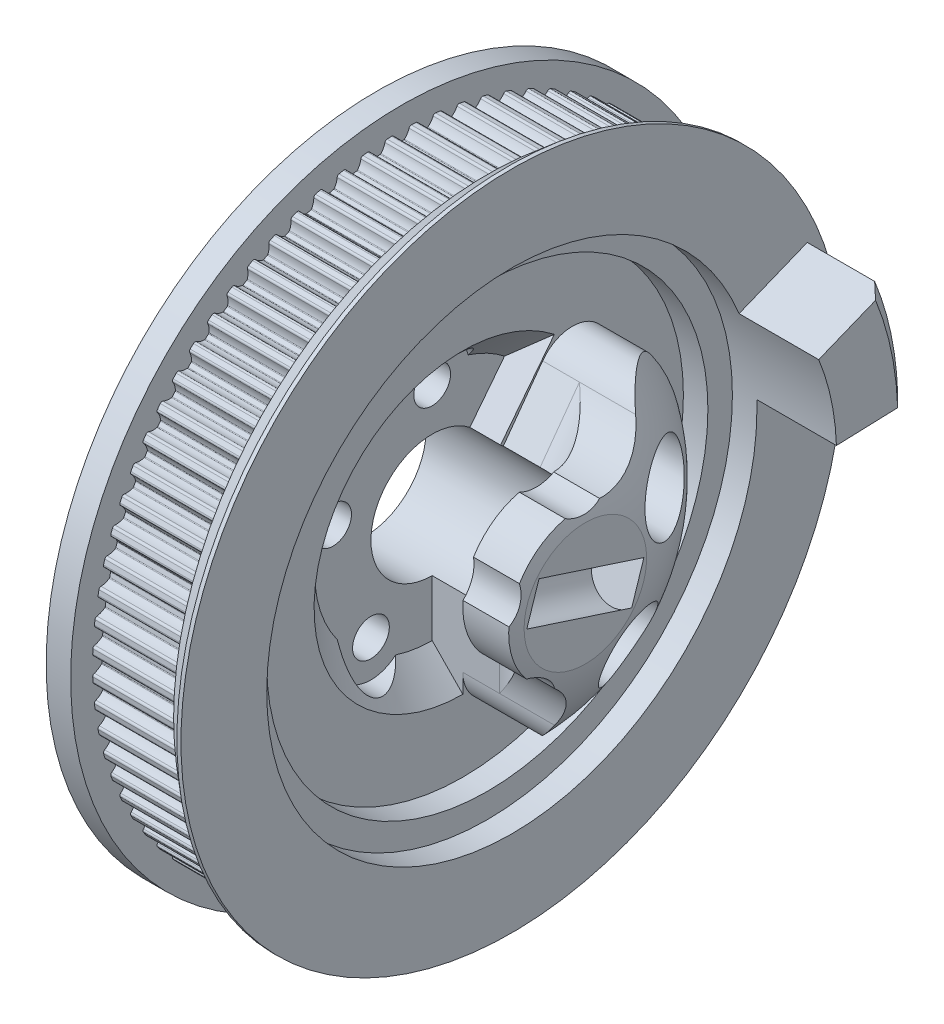
SolidWorks part; units mm, degrees
ref_plane "Front Plane" through (0, 0, 0) normal (0, 0, 1) x (1, 0, 0)
ref_plane "Top Plane" through (0, 0, 0) normal (0, 1, 0) x (1, 0, 0)
ref_plane "Right Plane" through (0, 0, 0) normal (1, 0, 0) x (0, 0, -1)
sketch "Sketch1" plane through (0, 0, 0) normal (0, 1, 0) x (1, 0, 0)
  line L0 (0, 5) -> (0, 15.5)
  line L1 (0, 15.5) -> (4, 15.5)
  line L2 (1, 23) -> (1, 27)
  line L3 (1, 27) -> (3, 27)
  line L4 (3, 27) -> (3, 23)
  line L5 (3, 23) -> (10, 23)
  line L6 (10, 23) -> (10, 27)
  line L7 (10, 27) -> (12, 27)
  line L8 (12, 27) -> (12, 20)
  line L11 (26, 0) -> (0, 0) construction
  line L12 (0, 5) -> (8, 5)
  line L13 (0, 0) -> (0, 5) construction
  line L14 (12, 20) -> (10, 20)
  line L15 (8, 18) -> (8, 5)
  line L17 (4, 15.5) -> (4, 21.3623)
  line L19 (1, 23) -> (1, 22.2508)
  line L20 (1, 22.2508) -> (4, 21.3623)
  arc A0 (10, 20) -> (8, 18) centre (10, 18) ccw
  point P17 (8, 20)
  dimension "D11" = 2
  dimension "D1" = 15.5
  dimension "D2" = 4
  dimension "D3" = 27
  dimension "D4" = 2
  dimension "D5" = 7
  dimension "D6" = 2
  dimension "D7" = 23
  dimension "D8" = 10
  dimension "D9" = 15
  dimension "D10" = 4
  dimension "D12" = 8
revolve "Revolve1" add sketch "Sketch1" angle 360 about L11
sketch "Sketch2" plane through (12, 0, 0) normal (1, 0, 0) x (0, 0, -1)
  line L0 (0, 0) -> (0, 8.5) construction
  circle A0 centre (0, 8.5) radius 1.5
  circle A1 centre (8.084, 2.6266) radius 1.5
  circle A2 centre (4.9962, -6.8766) radius 1.5
  circle A3 centre (-4.9962, -6.8766) radius 1.5
  circle A4 centre (-8.084, 2.6266) radius 1.5
  point P15 (0, 0)
  dimension "D2" = 3
  dimension "D1" = 8.5
extrude "Cut-Extrude1" cut sketch "Sketch2" against normal through all
chamfer "Chamfer1" distance 1 angle 45 1 edges at (0, 0, -15.5)
sketch "Sketch3" plane through (8, 0, 0) normal (1, 0, 0) x (0, 0, -1)
  circle A0 centre (0, 8.5) radius 3
  circle A1 centre (8.084, 2.6266) radius 3
  circle A2 centre (4.9962, -6.8766) radius 3
  circle A3 centre (-4.9962, -6.8766) radius 3
  circle A4 centre (-8.084, 2.6266) radius 3
  point P14 (0, 0)
  dimension "D1" = 6
extrude "Cut-Extrude2" cut sketch "Sketch3" against normal blind 2.5
sketch "Sketch4" plane through (8, 0, 0) normal (1, 0, 0) x (0, 0, -1)
  line L0 (3.3089, 3.7485) -> (6.518, 8.1654)
  line L1 (0, 9.099) -> (-8.6536, 2.8117) construction
  line L2 (-8.6536, 2.8117) -> (-5.3482, -7.3612) construction
  line L3 (-5.3482, -7.3612) -> (5.3482, -7.3612) construction
  line L4 (5.3482, -7.3612) -> (8.6536, 2.8117) construction
  line L5 (8.6536, 2.8117) -> (0, 9.099) construction
  line L6 (0, -5) -> (0, -10.583)
  circle A0 centre (0, 0) radius 7.3612 construction
  arc A1 (0, -5) -> (3.3089, 3.7485) centre (0, 0) ccw
  arc A2 (3.8182, -13.4693) -> (11.3846, 8.148) centre (0, 0) ccw
  arc A3 (0, -10.583) -> (3.8182, -13.4693) centre (3, -10.583) ccw
  arc A4 (6.518, 8.1654) -> (11.3846, 8.148) centre (8.9451, 6.402) cw
  circle A5 centre (0, 0) radius 5 construction
  point P14 (0, -14)
  dimension "D1" = 28
  dimension "D2" = 3
extrude "Boss-Extrude1" add sketch "Sketch4" along normal blind 6
sketch "Sketch5" plane through (14, 0, 0) normal (1, 0, 0) x (0, 0, -1)
  line L2 (6.518, 8.1654) -> (3.3089, 3.7485)
  line L3 (0, -5) -> (0, -10.583)
  arc A2 (1.0026, 5.9156) -> (-3.0811, -5.1485) centre (0, 0) ccw
  arc A3 (1.0026, 5.9156) -> (6.518, 8.1654) centre (1.9467, 11.4866) ccw
  arc A5 (-3.0811, -5.1485) -> (0, -10.583) centre (-6.3333, -10.583) cw
  arc A7 (0, -10.583) -> (3.8182, -13.4693) centre (3, -10.583) ccw
  arc A8 (3.8182, -13.4693) -> (11.3846, 8.148) centre (0, 0) ccw
  arc A9 (11.3846, 8.148) -> (6.518, 8.1654) centre (8.9451, 6.402) ccw
  arc A10 (0, -5) -> (3.3089, 3.7485) centre (0, 0) ccw
  arc A11 (0, -10.583) -> (3.8182, -13.4693) centre (3, -10.583) ccw
  arc A12 (3.8182, -13.4693) -> (11.3846, 8.148) centre (0, 0) ccw
  arc A13 (11.3846, 8.148) -> (6.518, 8.1654) centre (8.9451, 6.402) ccw
  dimension "D2" = 6
  dimension "D1" = 0
extrude "Boss-Extrude2" add sketch "Sketch5" along normal blind 4
sketch "Sketch7" plane through (18, 0, 0) normal (1, 0, 0) x (0, 0, -1)
  circle A0 centre (8.084, 2.6266) radius 1.5
  circle A1 centre (4.9962, -6.8766) radius 1.5
extrude "Cut-Extrude4" cut sketch "Sketch7" against normal through all
sketch "Sketch8" plane through (18, 0, 0) normal (1, 0, 0) x (0, 0, -1)
  circle A0 centre (8.084, 2.6266) radius 3
  circle A1 centre (4.9962, -6.8766) radius 3
  circle A2 centre (0, 8.5) radius 3
  circle A3 centre (-8.084, 2.6266) radius 3
  circle A4 centre (-4.9962, -6.8766) radius 3
  dimension "D1" = 6
  dimension "D2" = 6
  dimension "D3" = 6
  dimension "D4" = 6
  dimension "D5" = 6
extrude "Cut-Extrude5" cut sketch "Sketch8" against normal up to surface (12.5 mm away) up to face at (5.5, 8.5, -3)
sketch "Sketch9" plane through (0, 0, 0) normal (0, 1, 0) x (1, 0, 0)
  line L0 (0, 0) -> (18, 0) construction
  line L2 (18, 14) -> (8, 14) construction
  line L3 (12, 14) -> (18, 14)
  line L4 (18, 3.8182) -> (18, 14) construction
  line L5 (18, 14) -> (18, 5)
  arc A0 (12, 14) -> (18, 5) centre (3.5423, 1.8615) cw
  dimension "D1" = 9
  dimension "D2" = 6
revolve "Cut-Revolve1" cut sketch "Sketch9" angle 360 about L0
sketch "Sketch10" plane through (10, 0, 0) normal (-1, 0, 0) x (0, 0, 1)
  line L0 (0.1734, 24.4504) -> (-0.1734, 24.4504)
  line L1 (-0.8032, 25.1982) -> (-1.1763, 25.1835)
  line L2 (-1.7455, 24.3886) -> (-2.0913, 24.3614)
  line L3 (-2.7777, 25.0575) -> (-3.1486, 25.0136)
  line L4 (-3.6536, 24.1765) -> (-3.9962, 24.1222)
  line L5 (-4.7352, 24.7623) -> (-5.1014, 24.6895)
  line L6 (-5.5392, 23.8153) -> (-5.8765, 23.7343)
  line L7 (-6.6634, 24.3145) -> (-7.0228, 24.2131)
  line L8 (-7.3906, 23.3073) -> (-7.7205, 23.2001)
  line L9 (-8.5505, 23.7167) -> (-8.9009, 23.5875)
  line L10 (-9.1965, 22.6556) -> (-9.517, 22.5228)
  line L11 (-10.385, 22.9727) -> (-10.7241, 22.8164)
  line L12 (-10.9457, 21.8642) -> (-11.2548, 21.7067)
  line L13 (-12.1554, 22.0871) -> (-12.4812, 21.9047)
  line L14 (-12.6274, 20.938) -> (-12.9232, 20.7568)
  line L15 (-13.8508, 21.0653) -> (-14.1614, 20.8579)
  line L16 (-14.2313, 19.8827) -> (-14.5119, 19.6788)
  line L17 (-15.4609, 19.9137) -> (-15.7542, 19.6825)
  line L18 (-15.7474, 18.7049) -> (-16.0111, 18.4796)
  line L19 (-16.9757, 18.6392) -> (-17.2499, 18.3858)
  line L20 (-17.1664, 17.4117) -> (-17.4117, 17.1664)
  line L21 (-18.3858, 17.2499) -> (-18.6392, 16.9757)
  line L22 (-18.4796, 16.0111) -> (-18.7049, 15.7474)
  line L23 (-19.6825, 15.7542) -> (-19.9137, 15.4609)
  line L24 (-19.6788, 14.5119) -> (-19.8827, 14.2313)
  line L25 (-20.8579, 14.1614) -> (-21.0653, 13.8508)
  line L26 (-20.7568, 12.9232) -> (-20.938, 12.6274)
  line L27 (-21.9047, 12.4812) -> (-22.0871, 12.1554)
  line L28 (-21.7067, 11.2548) -> (-21.8642, 10.9457)
  line L29 (-22.8164, 10.7241) -> (-22.9727, 10.385)
  line L30 (-22.5228, 9.517) -> (-22.6556, 9.1965)
  line L31 (-23.5875, 8.9009) -> (-23.7167, 8.5505)
  line L32 (-23.2001, 7.7205) -> (-23.3073, 7.3906)
  line L33 (-24.2131, 7.0228) -> (-24.3145, 6.6634)
  line L34 (-23.7343, 5.8765) -> (-23.8153, 5.5392)
  line L35 (-24.6895, 5.1014) -> (-24.7623, 4.7352)
  line L36 (-24.1222, 3.9962) -> (-24.1765, 3.6536)
  line L37 (-25.0136, 3.1486) -> (-25.0575, 2.7777)
  line L38 (-24.3614, 2.0913) -> (-24.3886, 1.7455)
  line L39 (-25.1835, 1.1763) -> (-25.1982, 0.8032)
  line L40 (-24.4504, 0.1734) -> (-24.4504, -0.1734)
  line L41 (-25.1982, -0.8032) -> (-25.1835, -1.1763)
  line L42 (-24.3886, -1.7455) -> (-24.3614, -2.0913)
  line L43 (-25.0575, -2.7777) -> (-25.0136, -3.1486)
  line L44 (-24.1765, -3.6536) -> (-24.1222, -3.9962)
  line L45 (-24.7623, -4.7352) -> (-24.6895, -5.1014)
  line L46 (-23.8153, -5.5392) -> (-23.7343, -5.8765)
  line L47 (-24.3145, -6.6634) -> (-24.2131, -7.0228)
  line L48 (-23.3073, -7.3906) -> (-23.2001, -7.7205)
  line L49 (-23.7167, -8.5505) -> (-23.5875, -8.9009)
  line L50 (-22.6556, -9.1965) -> (-22.5228, -9.517)
  line L51 (-22.9727, -10.385) -> (-22.8164, -10.7241)
  line L52 (-21.8642, -10.9457) -> (-21.7067, -11.2548)
  line L53 (-22.0871, -12.1554) -> (-21.9047, -12.4812)
  line L54 (-20.938, -12.6274) -> (-20.7568, -12.9232)
  line L55 (-21.0653, -13.8508) -> (-20.8579, -14.1614)
  line L56 (-19.8827, -14.2313) -> (-19.6788, -14.5119)
  line L57 (-19.9137, -15.4609) -> (-19.6825, -15.7542)
  line L58 (-18.7049, -15.7474) -> (-18.4796, -16.0111)
  line L59 (-18.6392, -16.9757) -> (-18.3858, -17.2499)
  line L60 (-17.4117, -17.1664) -> (-17.1664, -17.4117)
  line L61 (-17.2499, -18.3858) -> (-16.9757, -18.6392)
  line L62 (-16.0111, -18.4796) -> (-15.7474, -18.7049)
  line L63 (-15.7542, -19.6825) -> (-15.4609, -19.9137)
  line L64 (-14.5119, -19.6788) -> (-14.2313, -19.8827)
  line L65 (-14.1614, -20.8579) -> (-13.8508, -21.0653)
  line L66 (-12.9232, -20.7568) -> (-12.6274, -20.938)
  line L67 (-12.4812, -21.9047) -> (-12.1554, -22.0871)
  line L68 (-11.2548, -21.7067) -> (-10.9457, -21.8642)
  line L69 (-10.7241, -22.8164) -> (-10.385, -22.9727)
  line L70 (-9.517, -22.5228) -> (-9.1965, -22.6556)
  line L71 (-8.9009, -23.5875) -> (-8.5505, -23.7167)
  line L72 (-7.7205, -23.2001) -> (-7.3906, -23.3073)
  line L73 (-7.0228, -24.2131) -> (-6.6634, -24.3145)
  line L74 (-5.8765, -23.7343) -> (-5.5392, -23.8153)
  line L75 (-5.1014, -24.6895) -> (-4.7352, -24.7623)
  line L76 (-3.9962, -24.1222) -> (-3.6536, -24.1765)
  line L77 (-3.1486, -25.0136) -> (-2.7777, -25.0575)
  line L78 (-2.0913, -24.3614) -> (-1.7455, -24.3886)
  line L79 (-1.1763, -25.1835) -> (-0.8032, -25.1982)
  line L80 (-0.1734, -24.4504) -> (0.1734, -24.4504)
  line L81 (0.8032, -25.1982) -> (1.1763, -25.1835)
  line L82 (1.7455, -24.3886) -> (2.0913, -24.3614)
  line L83 (2.7777, -25.0575) -> (3.1486, -25.0136)
  line L84 (3.6536, -24.1765) -> (3.9962, -24.1222)
  line L85 (4.7352, -24.7623) -> (5.1014, -24.6895)
  line L86 (5.5392, -23.8153) -> (5.8765, -23.7343)
  line L87 (6.6634, -24.3145) -> (7.0228, -24.2131)
  line L88 (7.3906, -23.3073) -> (7.7205, -23.2001)
  line L89 (8.5505, -23.7167) -> (8.9009, -23.5875)
  line L90 (9.1965, -22.6556) -> (9.517, -22.5228)
  line L91 (10.385, -22.9727) -> (10.7241, -22.8164)
  line L92 (10.9457, -21.8642) -> (11.2548, -21.7067)
  line L93 (12.1554, -22.0871) -> (12.4812, -21.9047)
  line L94 (12.6274, -20.938) -> (12.9232, -20.7568)
  line L95 (13.8508, -21.0653) -> (14.1614, -20.8579)
  line L96 (14.2313, -19.8827) -> (14.5119, -19.6788)
  line L97 (15.4609, -19.9137) -> (15.7542, -19.6825)
  line L98 (15.7474, -18.7049) -> (16.0111, -18.4796)
  line L99 (16.9757, -18.6392) -> (17.2499, -18.3858)
  line L100 (17.1664, -17.4117) -> (17.4117, -17.1664)
  line L101 (18.3858, -17.2499) -> (18.6392, -16.9757)
  line L102 (18.4796, -16.0111) -> (18.7049, -15.7474)
  line L103 (19.6825, -15.7542) -> (19.9137, -15.4609)
  line L104 (19.6788, -14.5119) -> (19.8827, -14.2313)
  line L105 (20.8579, -14.1614) -> (21.0653, -13.8508)
  line L106 (20.7568, -12.9232) -> (20.938, -12.6274)
  line L107 (21.9047, -12.4812) -> (22.0871, -12.1554)
  line L108 (21.7067, -11.2548) -> (21.8642, -10.9457)
  line L109 (22.8164, -10.7241) -> (22.9727, -10.385)
  line L110 (22.5228, -9.517) -> (22.6556, -9.1965)
  line L111 (23.5875, -8.9009) -> (23.7167, -8.5505)
  line L112 (23.2001, -7.7205) -> (23.3073, -7.3906)
  line L113 (24.2131, -7.0228) -> (24.3145, -6.6634)
  line L114 (23.7343, -5.8765) -> (23.8153, -5.5392)
  line L115 (24.6895, -5.1014) -> (24.7623, -4.7352)
  line L116 (24.1222, -3.9962) -> (24.1765, -3.6536)
  line L117 (25.0136, -3.1486) -> (25.0575, -2.7777)
  line L118 (24.3614, -2.0913) -> (24.3886, -1.7455)
  line L119 (25.1835, -1.1763) -> (25.1982, -0.8032)
  line L120 (24.4504, -0.1734) -> (24.4504, 0.1734)
  line L121 (25.1982, 0.8032) -> (25.1835, 1.1763)
  line L122 (24.3886, 1.7455) -> (24.3614, 2.0913)
  line L123 (25.0575, 2.7777) -> (25.0136, 3.1486)
  line L124 (24.1765, 3.6536) -> (24.1222, 3.9962)
  line L125 (24.7623, 4.7352) -> (24.6895, 5.1014)
  line L126 (23.8153, 5.5392) -> (23.7343, 5.8765)
  line L127 (24.3145, 6.6634) -> (24.2131, 7.0228)
  line L128 (23.3073, 7.3906) -> (23.2001, 7.7205)
  line L129 (23.7167, 8.5505) -> (23.5875, 8.9009)
  line L130 (22.6556, 9.1965) -> (22.5228, 9.517)
  line L131 (22.9727, 10.385) -> (22.8164, 10.7241)
  line L132 (21.8642, 10.9457) -> (21.7067, 11.2548)
  line L133 (22.0871, 12.1554) -> (21.9047, 12.4812)
  line L134 (20.938, 12.6274) -> (20.7568, 12.9232)
  line L135 (21.0653, 13.8508) -> (20.8579, 14.1614)
  line L136 (19.8827, 14.2313) -> (19.6788, 14.5119)
  line L137 (19.9137, 15.4609) -> (19.6825, 15.7542)
  line L138 (18.7049, 15.7474) -> (18.4796, 16.0111)
  line L139 (18.6392, 16.9757) -> (18.3858, 17.2499)
  line L140 (17.4117, 17.1664) -> (17.1664, 17.4117)
  line L141 (17.2499, 18.3858) -> (16.9757, 18.6392)
  line L142 (16.0111, 18.4796) -> (15.7474, 18.7049)
  line L143 (15.7542, 19.6825) -> (15.4609, 19.9137)
  line L144 (14.5119, 19.6788) -> (14.2313, 19.8827)
  line L145 (14.1614, 20.8579) -> (13.8508, 21.0653)
  line L146 (12.9232, 20.7568) -> (12.6274, 20.938)
  line L147 (12.4812, 21.9047) -> (12.1554, 22.0871)
  line L148 (11.2548, 21.7067) -> (10.9457, 21.8642)
  line L149 (10.7241, 22.8164) -> (10.385, 22.9727)
  line L150 (9.517, 22.5228) -> (9.1965, 22.6556)
  line L151 (8.9009, 23.5875) -> (8.5505, 23.7167)
  line L152 (7.7205, 23.2001) -> (7.3906, 23.3073)
  line L153 (7.0228, 24.2131) -> (6.6634, 24.3145)
  line L154 (5.8765, 23.7343) -> (5.5392, 23.8153)
  line L155 (5.1014, 24.6895) -> (4.7352, 24.7623)
  line L156 (3.9962, 24.1222) -> (3.6536, 24.1765)
  line L157 (3.1486, 25.0136) -> (2.7777, 25.0575)
  line L158 (2.0913, 24.3614) -> (1.7455, 24.3886)
  circle A0 centre (0, 0) radius 18
  arc A1 (0.8032, 25.1982) -> (0.6156, 25.0645) centre (0.7971, 25.0083) ccw
  arc A2 (0.2414, 24.4764) -> (0.6156, 25.0645) centre (-0.65, 25.4567) ccw
  arc A3 (0.1734, 24.4504) -> (0.2414, 24.4764) centre (0.1741, 24.5504) ccw
  arc A4 (-0.2414, 24.4764) -> (-0.1734, 24.4504) centre (-0.1741, 24.5504) ccw
  arc A5 (-0.6156, 25.0645) -> (-0.2414, 24.4764) centre (0.65, 25.4567) ccw
  arc A6 (-0.6156, 25.0645) -> (-0.8032, 25.1982) centre (-0.7971, 25.0083) ccw
  arc A7 (-1.1763, 25.1835) -> (-1.3528, 25.0356) centre (-1.1675, 24.9937) ccw
  arc A8 (-1.6797, 24.4199) -> (-1.3528, 25.0356) centre (-2.6453, 25.3272) ccw
  arc A9 (-1.7455, 24.3886) -> (-1.6797, 24.4199) centre (-1.7526, 24.4884) ccw
  arc A10 (-2.1611, 24.382) -> (-2.0913, 24.3614) centre (-2.0998, 24.461) ccw
  arc A11 (-2.5803, 24.939) -> (-2.1611, 24.382) centre (-1.3493, 25.4292) ccw
  arc A12 (-2.5803, 24.939) -> (-2.7777, 25.0575) centre (-2.7568, 24.8687) ccw
  arc A13 (-3.1486, 25.0136) -> (-3.3129, 24.8523) centre (-3.1249, 24.8251) ccw
  arc A14 (-3.5905, 24.2128) -> (-3.3129, 24.8523) centre (-4.6243, 25.0416) ccw
  arc A15 (-3.6536, 24.1765) -> (-3.5905, 24.2128) centre (-3.6685, 24.2754) ccw
  arc A16 (-4.0674, 24.1373) -> (-3.9962, 24.1222) centre (-4.0125, 24.2209) ccw
  arc A17 (-4.529, 24.6596) -> (-4.0674, 24.1373) centre (-3.3403, 25.245) ccw
  arc A18 (-4.529, 24.6596) -> (-4.7352, 24.7623) centre (-4.6995, 24.5757) ccw
  arc A19 (-5.1014, 24.6895) -> (-5.2526, 24.5157) centre (-5.063, 24.5034) ccw
  arc A20 (-5.4792, 23.8565) -> (-5.2526, 24.5157) centre (-6.5748, 24.6016) ccw
  arc A21 (-5.5392, 23.8153) -> (-5.4792, 23.8565) centre (-5.5618, 23.9127) ccw
  arc A22 (-5.9486, 23.7438) -> (-5.8765, 23.7343) centre (-5.9005, 23.8314) ccw
  arc A23 (-6.4498, 24.2283) -> (-5.9486, 23.7438) centre (-5.3107, 24.9051) ccw
  arc A24 (-6.4498, 24.2283) -> (-6.6634, 24.3145) centre (-6.6132, 24.1312) ccw
  arc A25 (-7.0228, 24.2131) -> (-7.1599, 24.028) centre (-6.9699, 24.0306) ccw
  arc A26 (-7.334, 23.353) -> (-7.1599, 24.028) centre (-8.4847, 24.0099) ccw
  arc A27 (-7.3906, 23.3073) -> (-7.334, 23.353) centre (-7.4209, 23.4026) ccw
  arc A28 (-7.7932, 23.2038) -> (-7.7205, 23.2001) centre (-7.7521, 23.295) ccw
  arc A29 (-8.3309, 23.6475) -> (-7.7932, 23.2038) centre (-7.2484, 24.4116) ccw
  arc A30 (-8.3309, 23.6475) -> (-8.5505, 23.7167) centre (-8.4861, 23.538) ccw
  arc A31 (-8.9009, 23.5875) -> (-9.023, 23.3922) centre (-8.8338, 23.4097) ccw
  arc A32 (-9.1437, 22.7056) -> (-9.023, 23.3922) centre (-10.3424, 23.2702) ccw
  arc A33 (-9.1965, 22.6556) -> (-9.1437, 22.7056) centre (-9.2341, 22.7482) ccw
  arc A34 (-9.5898, 22.5209) -> (-9.517, 22.5228) centre (-9.5559, 22.615) ccw
  arc A35 (-10.1606, 22.921) -> (-9.5898, 22.5209) centre (-9.1413, 23.7677) ccw
  arc A36 (-10.1606, 22.921) -> (-10.385, 22.9727) centre (-10.3067, 22.7996) ccw
  arc A37 (-10.7241, 22.8164) -> (-10.8305, 22.6122) centre (-10.6433, 22.6444) ccw
  arc A38 (-10.8969, 21.9182) -> (-10.8305, 22.6122) centre (-12.1363, 22.387) ccw
  arc A39 (-10.9457, 21.8642) -> (-10.8969, 21.9182) centre (-10.9905, 21.9536) ccw
  arc A40 (-11.3272, 21.699) -> (-11.2548, 21.7067) centre (-11.3008, 21.7955) ccw
  arc A41 (-11.9276, 22.0532) -> (-11.3272, 21.699) centre (-10.9779, 22.9772) ccw
  arc A42 (-11.9276, 22.0532) -> (-12.1554, 22.0871) centre (-12.0638, 21.9207) ccw
  arc A43 (-12.4812, 21.9047) -> (-12.5713, 21.6927) centre (-12.3871, 21.7396) ccw
  arc A44 (-12.583, 20.9957) -> (-12.5713, 21.6927) centre (-13.8553, 21.3658) ccw
  arc A45 (-12.6274, 20.938) -> (-12.583, 20.9957) centre (-12.6791, 21.0236) ccw
  arc A46 (-12.9947, 20.7434) -> (-12.9232, 20.7568) centre (-12.976, 20.8417) ccw
  arc A47 (-13.6211, 21.0494) -> (-12.9947, 20.7434) centre (-12.7469, 22.045) ccw
  arc A48 (-13.6211, 21.0494) -> (-13.8508, 21.0653) centre (-13.7465, 20.9066) ccw
  arc A49 (-14.1614, 20.8579) -> (-14.2345, 20.6395) centre (-14.0546, 20.7007) ccw
  arc A50 (-14.1916, 19.9437) -> (-14.2345, 20.6395) centre (-15.4889, 20.2128) ccw
  arc A51 (-14.2313, 19.8827) -> (-14.1916, 19.9437) centre (-14.2895, 19.964) ccw
  arc A52 (-14.5822, 19.6599) -> (-14.5119, 19.6788) centre (-14.5712, 19.7593) ccw
  arc A53 (-15.2306, 19.9158) -> (-14.5822, 19.6599) centre (-14.4372, 20.977) ccw
  arc A54 (-15.2306, 19.9158) -> (-15.4609, 19.9137) centre (-15.3444, 19.7636) ccw
  arc A55 (-15.7542, 19.6825) -> (-15.81, 19.459) centre (-15.6355, 19.5341) ccw
  arc A56 (-15.7126, 18.7688) -> (-15.81, 19.459) centre (-17.0271, 18.9353) ccw
  arc A57 (-15.7474, 18.7049) -> (-15.7126, 18.7688) centre (-15.8118, 18.7814) ccw
  arc A58 (-16.0797, 18.4552) -> (-16.0111, 18.4796) centre (-16.0766, 18.5552) ccw
  arc A59 (-16.7462, 18.6594) -> (-16.0797, 18.4552) centre (-16.0385, 19.7796) ccw
  arc A60 (-16.7462, 18.6594) -> (-16.9757, 18.6392) centre (-16.8477, 18.4988) ccw
  arc A61 (-17.2499, 18.3858) -> (-17.288, 18.1586) centre (-17.1199, 18.2472) ccw
  arc A62 (-17.1367, 17.4781) -> (-17.288, 18.1586) centre (-18.4602, 17.541) ccw
  arc A63 (-17.1664, 17.4117) -> (-17.1367, 17.4781) centre (-17.2366, 17.4829) ccw
  arc A64 (-17.4781, 17.1367) -> (-17.4117, 17.1664) centre (-17.4829, 17.2366) ccw
  arc A65 (-18.1586, 17.288) -> (-17.4781, 17.1367) centre (-17.541, 18.4602) ccw
  arc A66 (-18.1586, 17.288) -> (-18.3858, 17.2499) centre (-18.2472, 17.1199) ccw
  arc A67 (-18.6392, 16.9757) -> (-18.6594, 16.7462) centre (-18.4988, 16.8477) ccw
  arc A68 (-18.4552, 16.0797) -> (-18.6594, 16.7462) centre (-19.7796, 16.0385) ccw
  arc A69 (-18.4796, 16.0111) -> (-18.4552, 16.0797) centre (-18.5552, 16.0766) ccw
  arc A70 (-18.7688, 15.7126) -> (-18.7049, 15.7474) centre (-18.7814, 15.8118) ccw
  arc A71 (-19.459, 15.81) -> (-18.7688, 15.7126) centre (-18.9353, 17.0271) ccw
  arc A72 (-19.459, 15.81) -> (-19.6825, 15.7542) centre (-19.5341, 15.6355) ccw
  arc A73 (-19.9137, 15.4609) -> (-19.9158, 15.2306) centre (-19.7636, 15.3444) ccw
  arc A74 (-19.6599, 14.5822) -> (-19.9158, 15.2306) centre (-20.977, 14.4372) ccw
  arc A75 (-19.6788, 14.5119) -> (-19.6599, 14.5822) centre (-19.7593, 14.5712) ccw
  arc A76 (-19.9437, 14.1916) -> (-19.8827, 14.2313) centre (-19.964, 14.2895) ccw
  arc A77 (-20.6395, 14.2345) -> (-19.9437, 14.1916) centre (-20.2128, 15.4889) ccw
  arc A78 (-20.6395, 14.2345) -> (-20.8579, 14.1614) centre (-20.7007, 14.0546) ccw
  arc A79 (-21.0653, 13.8508) -> (-21.0494, 13.6211) centre (-20.9066, 13.7465) ccw
  arc A80 (-20.7434, 12.9947) -> (-21.0494, 13.6211) centre (-22.045, 12.7469) ccw
  arc A81 (-20.7568, 12.9232) -> (-20.7434, 12.9947) centre (-20.8417, 12.976) ccw
  arc A82 (-20.9957, 12.583) -> (-20.938, 12.6274) centre (-21.0236, 12.6791) ccw
  arc A83 (-21.6927, 12.5713) -> (-20.9957, 12.583) centre (-21.3658, 13.8553) ccw
  arc A84 (-21.6927, 12.5713) -> (-21.9047, 12.4812) centre (-21.7396, 12.3871) ccw
  arc A85 (-22.0871, 12.1554) -> (-22.0532, 11.9276) centre (-21.9207, 12.0638) ccw
  arc A86 (-21.699, 11.3272) -> (-22.0532, 11.9276) centre (-22.9772, 10.9779) ccw
  arc A87 (-21.7067, 11.2548) -> (-21.699, 11.3272) centre (-21.7955, 11.3008) ccw
  arc A88 (-21.9182, 10.8969) -> (-21.8642, 10.9457) centre (-21.9536, 10.9905) ccw
  arc A89 (-22.6122, 10.8305) -> (-21.9182, 10.8969) centre (-22.387, 12.1363) ccw
  arc A90 (-22.6122, 10.8305) -> (-22.8164, 10.7241) centre (-22.6444, 10.6433) ccw
  arc A91 (-22.9727, 10.385) -> (-22.921, 10.1606) centre (-22.7996, 10.3067) ccw
  arc A92 (-22.5209, 9.5898) -> (-22.921, 10.1606) centre (-23.7677, 9.1413) ccw
  arc A93 (-22.5228, 9.517) -> (-22.5209, 9.5898) centre (-22.615, 9.5559) ccw
  arc A94 (-22.7056, 9.1437) -> (-22.6556, 9.1965) centre (-22.7482, 9.2341) ccw
  arc A95 (-23.3922, 9.023) -> (-22.7056, 9.1437) centre (-23.2702, 10.3424) ccw
  arc A96 (-23.3922, 9.023) -> (-23.5875, 8.9009) centre (-23.4097, 8.8338) ccw
  arc A97 (-23.7167, 8.5505) -> (-23.6475, 8.3309) centre (-23.538, 8.4861) ccw
  arc A98 (-23.2038, 7.7932) -> (-23.6475, 8.3309) centre (-24.4116, 7.2484) ccw
  arc A99 (-23.2001, 7.7205) -> (-23.2038, 7.7932) centre (-23.295, 7.7521) ccw
  arc A100 (-23.353, 7.334) -> (-23.3073, 7.3906) centre (-23.4026, 7.4209) ccw
  arc A101 (-24.028, 7.1599) -> (-23.353, 7.334) centre (-24.0099, 8.4847) ccw
  arc A102 (-24.028, 7.1599) -> (-24.2131, 7.0228) centre (-24.0306, 6.9699) ccw
  arc A103 (-24.3145, 6.6634) -> (-24.2283, 6.4498) centre (-24.1312, 6.6132) ccw
  arc A104 (-23.7438, 5.9486) -> (-24.2283, 6.4498) centre (-24.9051, 5.3107) ccw
  arc A105 (-23.7343, 5.8765) -> (-23.7438, 5.9486) centre (-23.8314, 5.9005) ccw
  arc A106 (-23.8565, 5.4792) -> (-23.8153, 5.5392) centre (-23.9127, 5.5618) ccw
  arc A107 (-24.5157, 5.2526) -> (-23.8565, 5.4792) centre (-24.6016, 6.5748) ccw
  arc A108 (-24.5157, 5.2526) -> (-24.6895, 5.1014) centre (-24.5034, 5.063) ccw
  arc A109 (-24.7623, 4.7352) -> (-24.6596, 4.529) centre (-24.5757, 4.6995) ccw
  arc A110 (-24.1373, 4.0674) -> (-24.6596, 4.529) centre (-25.245, 3.3403) ccw
  arc A111 (-24.1222, 3.9962) -> (-24.1373, 4.0674) centre (-24.2209, 4.0125) ccw
  arc A112 (-24.2128, 3.5905) -> (-24.1765, 3.6536) centre (-24.2754, 3.6685) ccw
  arc A113 (-24.8523, 3.3129) -> (-24.2128, 3.5905) centre (-25.0416, 4.6243) ccw
  arc A114 (-24.8523, 3.3129) -> (-25.0136, 3.1486) centre (-24.8251, 3.1249) ccw
  arc A115 (-25.0575, 2.7777) -> (-24.939, 2.5803) centre (-24.8687, 2.7568) ccw
  arc A116 (-24.382, 2.1611) -> (-24.939, 2.5803) centre (-25.4292, 1.3493) ccw
  arc A117 (-24.3614, 2.0913) -> (-24.382, 2.1611) centre (-24.461, 2.0998) ccw
  arc A118 (-24.4199, 1.6797) -> (-24.3886, 1.7455) centre (-24.4884, 1.7526) ccw
  arc A119 (-25.0356, 1.3528) -> (-24.4199, 1.6797) centre (-25.3272, 2.6453) ccw
  arc A120 (-25.0356, 1.3528) -> (-25.1835, 1.1763) centre (-24.9937, 1.1675) ccw
  arc A121 (-25.1982, 0.8032) -> (-25.0645, 0.6156) centre (-25.0083, 0.7971) ccw
  arc A122 (-24.4764, 0.2414) -> (-25.0645, 0.6156) centre (-25.4567, -0.65) ccw
  arc A123 (-24.4504, 0.1734) -> (-24.4764, 0.2414) centre (-24.5504, 0.1741) ccw
  arc A124 (-24.4764, -0.2414) -> (-24.4504, -0.1734) centre (-24.5504, -0.1741) ccw
  arc A125 (-25.0645, -0.6156) -> (-24.4764, -0.2414) centre (-25.4567, 0.65) ccw
  arc A126 (-25.0645, -0.6156) -> (-25.1982, -0.8032) centre (-25.0083, -0.7971) ccw
  arc A127 (-25.1835, -1.1763) -> (-25.0356, -1.3528) centre (-24.9937, -1.1675) ccw
  arc A128 (-24.4199, -1.6797) -> (-25.0356, -1.3528) centre (-25.3272, -2.6453) ccw
  arc A129 (-24.3886, -1.7455) -> (-24.4199, -1.6797) centre (-24.4884, -1.7526) ccw
  arc A130 (-24.382, -2.1611) -> (-24.3614, -2.0913) centre (-24.461, -2.0998) ccw
  arc A131 (-24.939, -2.5803) -> (-24.382, -2.1611) centre (-25.4292, -1.3493) ccw
  arc A132 (-24.939, -2.5803) -> (-25.0575, -2.7777) centre (-24.8687, -2.7568) ccw
  arc A133 (-25.0136, -3.1486) -> (-24.8523, -3.3129) centre (-24.8251, -3.1249) ccw
  arc A134 (-24.2128, -3.5905) -> (-24.8523, -3.3129) centre (-25.0416, -4.6243) ccw
  arc A135 (-24.1765, -3.6536) -> (-24.2128, -3.5905) centre (-24.2754, -3.6685) ccw
  arc A136 (-24.1373, -4.0674) -> (-24.1222, -3.9962) centre (-24.2209, -4.0125) ccw
  arc A137 (-24.6596, -4.529) -> (-24.1373, -4.0674) centre (-25.245, -3.3403) ccw
  arc A138 (-24.6596, -4.529) -> (-24.7623, -4.7352) centre (-24.5757, -4.6995) ccw
  arc A139 (-24.6895, -5.1014) -> (-24.5157, -5.2526) centre (-24.5034, -5.063) ccw
  arc A140 (-23.8565, -5.4792) -> (-24.5157, -5.2526) centre (-24.6016, -6.5748) ccw
  arc A141 (-23.8153, -5.5392) -> (-23.8565, -5.4792) centre (-23.9127, -5.5618) ccw
  arc A142 (-23.7438, -5.9486) -> (-23.7343, -5.8765) centre (-23.8314, -5.9005) ccw
  arc A143 (-24.2283, -6.4498) -> (-23.7438, -5.9486) centre (-24.9051, -5.3107) ccw
  arc A144 (-24.2283, -6.4498) -> (-24.3145, -6.6634) centre (-24.1312, -6.6132) ccw
  arc A145 (-24.2131, -7.0228) -> (-24.028, -7.1599) centre (-24.0306, -6.9699) ccw
  arc A146 (-23.353, -7.334) -> (-24.028, -7.1599) centre (-24.0099, -8.4847) ccw
  arc A147 (-23.3073, -7.3906) -> (-23.353, -7.334) centre (-23.4026, -7.4209) ccw
  arc A148 (-23.2038, -7.7932) -> (-23.2001, -7.7205) centre (-23.295, -7.7521) ccw
  arc A149 (-23.6475, -8.3309) -> (-23.2038, -7.7932) centre (-24.4116, -7.2484) ccw
  arc A150 (-23.6475, -8.3309) -> (-23.7167, -8.5505) centre (-23.538, -8.4861) ccw
  arc A151 (-23.5875, -8.9009) -> (-23.3922, -9.023) centre (-23.4097, -8.8338) ccw
  arc A152 (-22.7056, -9.1437) -> (-23.3922, -9.023) centre (-23.2702, -10.3424) ccw
  arc A153 (-22.6556, -9.1965) -> (-22.7056, -9.1437) centre (-22.7482, -9.2341) ccw
  arc A154 (-22.5209, -9.5898) -> (-22.5228, -9.517) centre (-22.615, -9.5559) ccw
  arc A155 (-22.921, -10.1606) -> (-22.5209, -9.5898) centre (-23.7677, -9.1413) ccw
  arc A156 (-22.921, -10.1606) -> (-22.9727, -10.385) centre (-22.7996, -10.3067) ccw
  arc A157 (-22.8164, -10.7241) -> (-22.6122, -10.8305) centre (-22.6444, -10.6433) ccw
  arc A158 (-21.9182, -10.8969) -> (-22.6122, -10.8305) centre (-22.387, -12.1363) ccw
  arc A159 (-21.8642, -10.9457) -> (-21.9182, -10.8969) centre (-21.9536, -10.9905) ccw
  arc A160 (-21.699, -11.3272) -> (-21.7067, -11.2548) centre (-21.7955, -11.3008) ccw
  arc A161 (-22.0532, -11.9276) -> (-21.699, -11.3272) centre (-22.9772, -10.9779) ccw
  arc A162 (-22.0532, -11.9276) -> (-22.0871, -12.1554) centre (-21.9207, -12.0638) ccw
  arc A163 (-21.9047, -12.4812) -> (-21.6927, -12.5713) centre (-21.7396, -12.3871) ccw
  arc A164 (-20.9957, -12.583) -> (-21.6927, -12.5713) centre (-21.3658, -13.8553) ccw
  arc A165 (-20.938, -12.6274) -> (-20.9957, -12.583) centre (-21.0236, -12.6791) ccw
  arc A166 (-20.7434, -12.9947) -> (-20.7568, -12.9232) centre (-20.8417, -12.976) ccw
  arc A167 (-21.0494, -13.6211) -> (-20.7434, -12.9947) centre (-22.045, -12.7469) ccw
  arc A168 (-21.0494, -13.6211) -> (-21.0653, -13.8508) centre (-20.9066, -13.7465) ccw
  arc A169 (-20.8579, -14.1614) -> (-20.6395, -14.2345) centre (-20.7007, -14.0546) ccw
  arc A170 (-19.9437, -14.1916) -> (-20.6395, -14.2345) centre (-20.2128, -15.4889) ccw
  arc A171 (-19.8827, -14.2313) -> (-19.9437, -14.1916) centre (-19.964, -14.2895) ccw
  arc A172 (-19.6599, -14.5822) -> (-19.6788, -14.5119) centre (-19.7593, -14.5712) ccw
  arc A173 (-19.9158, -15.2306) -> (-19.6599, -14.5822) centre (-20.977, -14.4372) ccw
  arc A174 (-19.9158, -15.2306) -> (-19.9137, -15.4609) centre (-19.7636, -15.3444) ccw
  arc A175 (-19.6825, -15.7542) -> (-19.459, -15.81) centre (-19.5341, -15.6355) ccw
  arc A176 (-18.7688, -15.7126) -> (-19.459, -15.81) centre (-18.9353, -17.0271) ccw
  arc A177 (-18.7049, -15.7474) -> (-18.7688, -15.7126) centre (-18.7814, -15.8118) ccw
  arc A178 (-18.4552, -16.0797) -> (-18.4796, -16.0111) centre (-18.5552, -16.0766) ccw
  arc A179 (-18.6594, -16.7462) -> (-18.4552, -16.0797) centre (-19.7796, -16.0385) ccw
  arc A180 (-18.6594, -16.7462) -> (-18.6392, -16.9757) centre (-18.4988, -16.8477) ccw
  arc A181 (-18.3858, -17.2499) -> (-18.1586, -17.288) centre (-18.2472, -17.1199) ccw
  arc A182 (-17.4781, -17.1367) -> (-18.1586, -17.288) centre (-17.541, -18.4602) ccw
  arc A183 (-17.4117, -17.1664) -> (-17.4781, -17.1367) centre (-17.4829, -17.2366) ccw
  arc A184 (-17.1367, -17.4781) -> (-17.1664, -17.4117) centre (-17.2366, -17.4829) ccw
  arc A185 (-17.288, -18.1586) -> (-17.1367, -17.4781) centre (-18.4602, -17.541) ccw
  arc A186 (-17.288, -18.1586) -> (-17.2499, -18.3858) centre (-17.1199, -18.2472) ccw
  arc A187 (-16.9757, -18.6392) -> (-16.7462, -18.6594) centre (-16.8477, -18.4988) ccw
  arc A188 (-16.0797, -18.4552) -> (-16.7462, -18.6594) centre (-16.0385, -19.7796) ccw
  arc A189 (-16.0111, -18.4796) -> (-16.0797, -18.4552) centre (-16.0766, -18.5552) ccw
  arc A190 (-15.7126, -18.7688) -> (-15.7474, -18.7049) centre (-15.8118, -18.7814) ccw
  arc A191 (-15.81, -19.459) -> (-15.7126, -18.7688) centre (-17.0271, -18.9353) ccw
  arc A192 (-15.81, -19.459) -> (-15.7542, -19.6825) centre (-15.6355, -19.5341) ccw
  arc A193 (-15.4609, -19.9137) -> (-15.2306, -19.9158) centre (-15.3444, -19.7636) ccw
  arc A194 (-14.5822, -19.6599) -> (-15.2306, -19.9158) centre (-14.4372, -20.977) ccw
  arc A195 (-14.5119, -19.6788) -> (-14.5822, -19.6599) centre (-14.5712, -19.7593) ccw
  arc A196 (-14.1916, -19.9437) -> (-14.2313, -19.8827) centre (-14.2895, -19.964) ccw
  arc A197 (-14.2345, -20.6395) -> (-14.1916, -19.9437) centre (-15.4889, -20.2128) ccw
  arc A198 (-14.2345, -20.6395) -> (-14.1614, -20.8579) centre (-14.0546, -20.7007) ccw
  arc A199 (-13.8508, -21.0653) -> (-13.6211, -21.0494) centre (-13.7465, -20.9066) ccw
  arc A200 (-12.9947, -20.7434) -> (-13.6211, -21.0494) centre (-12.7469, -22.045) ccw
  arc A201 (-12.9232, -20.7568) -> (-12.9947, -20.7434) centre (-12.976, -20.8417) ccw
  arc A202 (-12.583, -20.9957) -> (-12.6274, -20.938) centre (-12.6791, -21.0236) ccw
  arc A203 (-12.5713, -21.6927) -> (-12.583, -20.9957) centre (-13.8553, -21.3658) ccw
  arc A204 (-12.5713, -21.6927) -> (-12.4812, -21.9047) centre (-12.3871, -21.7396) ccw
  arc A205 (-12.1554, -22.0871) -> (-11.9276, -22.0532) centre (-12.0638, -21.9207) ccw
  arc A206 (-11.3272, -21.699) -> (-11.9276, -22.0532) centre (-10.9779, -22.9772) ccw
  arc A207 (-11.2548, -21.7067) -> (-11.3272, -21.699) centre (-11.3008, -21.7955) ccw
  arc A208 (-10.8969, -21.9182) -> (-10.9457, -21.8642) centre (-10.9905, -21.9536) ccw
  arc A209 (-10.8305, -22.6122) -> (-10.8969, -21.9182) centre (-12.1363, -22.387) ccw
  arc A210 (-10.8305, -22.6122) -> (-10.7241, -22.8164) centre (-10.6433, -22.6444) ccw
  arc A211 (-10.385, -22.9727) -> (-10.1606, -22.921) centre (-10.3067, -22.7996) ccw
  arc A212 (-9.5898, -22.5209) -> (-10.1606, -22.921) centre (-9.1413, -23.7677) ccw
  arc A213 (-9.517, -22.5228) -> (-9.5898, -22.5209) centre (-9.5559, -22.615) ccw
  arc A214 (-9.1437, -22.7056) -> (-9.1965, -22.6556) centre (-9.2341, -22.7482) ccw
  arc A215 (-9.023, -23.3922) -> (-9.1437, -22.7056) centre (-10.3424, -23.2702) ccw
  arc A216 (-9.023, -23.3922) -> (-8.9009, -23.5875) centre (-8.8338, -23.4097) ccw
  arc A217 (-8.5505, -23.7167) -> (-8.3309, -23.6475) centre (-8.4861, -23.538) ccw
  arc A218 (-7.7932, -23.2038) -> (-8.3309, -23.6475) centre (-7.2484, -24.4116) ccw
  arc A219 (-7.7205, -23.2001) -> (-7.7932, -23.2038) centre (-7.7521, -23.295) ccw
  arc A220 (-7.334, -23.353) -> (-7.3906, -23.3073) centre (-7.4209, -23.4026) ccw
  arc A221 (-7.1599, -24.028) -> (-7.334, -23.353) centre (-8.4847, -24.0099) ccw
  arc A222 (-7.1599, -24.028) -> (-7.0228, -24.2131) centre (-6.9699, -24.0306) ccw
  arc A223 (-6.6634, -24.3145) -> (-6.4498, -24.2283) centre (-6.6132, -24.1312) ccw
  arc A224 (-5.9486, -23.7438) -> (-6.4498, -24.2283) centre (-5.3107, -24.9051) ccw
  arc A225 (-5.8765, -23.7343) -> (-5.9486, -23.7438) centre (-5.9005, -23.8314) ccw
  arc A226 (-5.4792, -23.8565) -> (-5.5392, -23.8153) centre (-5.5618, -23.9127) ccw
  arc A227 (-5.2526, -24.5157) -> (-5.4792, -23.8565) centre (-6.5748, -24.6016) ccw
  arc A228 (-5.2526, -24.5157) -> (-5.1014, -24.6895) centre (-5.063, -24.5034) ccw
  arc A229 (-4.7352, -24.7623) -> (-4.529, -24.6596) centre (-4.6995, -24.5757) ccw
  arc A230 (-4.0674, -24.1373) -> (-4.529, -24.6596) centre (-3.3403, -25.245) ccw
  arc A231 (-3.9962, -24.1222) -> (-4.0674, -24.1373) centre (-4.0125, -24.2209) ccw
  arc A232 (-3.5905, -24.2128) -> (-3.6536, -24.1765) centre (-3.6685, -24.2754) ccw
  arc A233 (-3.3129, -24.8523) -> (-3.5905, -24.2128) centre (-4.6243, -25.0416) ccw
  arc A234 (-3.3129, -24.8523) -> (-3.1486, -25.0136) centre (-3.1249, -24.8251) ccw
  arc A235 (-2.7777, -25.0575) -> (-2.5803, -24.939) centre (-2.7568, -24.8687) ccw
  arc A236 (-2.1611, -24.382) -> (-2.5803, -24.939) centre (-1.3493, -25.4292) ccw
  arc A237 (-2.0913, -24.3614) -> (-2.1611, -24.382) centre (-2.0998, -24.461) ccw
  arc A238 (-1.6797, -24.4199) -> (-1.7455, -24.3886) centre (-1.7526, -24.4884) ccw
  arc A239 (-1.3528, -25.0356) -> (-1.6797, -24.4199) centre (-2.6453, -25.3272) ccw
  arc A240 (-1.3528, -25.0356) -> (-1.1763, -25.1835) centre (-1.1675, -24.9937) ccw
  arc A241 (-0.8032, -25.1982) -> (-0.6156, -25.0645) centre (-0.7971, -25.0083) ccw
  arc A242 (-0.2414, -24.4764) -> (-0.6156, -25.0645) centre (0.65, -25.4567) ccw
  arc A243 (-0.1734, -24.4504) -> (-0.2414, -24.4764) centre (-0.1741, -24.5504) ccw
  arc A244 (0.2414, -24.4764) -> (0.1734, -24.4504) centre (0.1741, -24.5504) ccw
  arc A245 (0.6156, -25.0645) -> (0.2414, -24.4764) centre (-0.65, -25.4567) ccw
  arc A246 (0.6156, -25.0645) -> (0.8032, -25.1982) centre (0.7971, -25.0083) ccw
  arc A247 (1.1763, -25.1835) -> (1.3528, -25.0356) centre (1.1675, -24.9937) ccw
  arc A248 (1.6797, -24.4199) -> (1.3528, -25.0356) centre (2.6453, -25.3272) ccw
  arc A249 (1.7455, -24.3886) -> (1.6797, -24.4199) centre (1.7526, -24.4884) ccw
  arc A250 (2.1611, -24.382) -> (2.0913, -24.3614) centre (2.0998, -24.461) ccw
  arc A251 (2.5803, -24.939) -> (2.1611, -24.382) centre (1.3493, -25.4292) ccw
  arc A252 (2.5803, -24.939) -> (2.7777, -25.0575) centre (2.7568, -24.8687) ccw
  arc A253 (3.1486, -25.0136) -> (3.3129, -24.8523) centre (3.1249, -24.8251) ccw
  arc A254 (3.5905, -24.2128) -> (3.3129, -24.8523) centre (4.6243, -25.0416) ccw
  arc A255 (3.6536, -24.1765) -> (3.5905, -24.2128) centre (3.6685, -24.2754) ccw
  arc A256 (4.0674, -24.1373) -> (3.9962, -24.1222) centre (4.0125, -24.2209) ccw
  arc A257 (4.529, -24.6596) -> (4.0674, -24.1373) centre (3.3403, -25.245) ccw
  arc A258 (4.529, -24.6596) -> (4.7352, -24.7623) centre (4.6995, -24.5757) ccw
  arc A259 (5.1014, -24.6895) -> (5.2526, -24.5157) centre (5.063, -24.5034) ccw
  arc A260 (5.4792, -23.8565) -> (5.2526, -24.5157) centre (6.5748, -24.6016) ccw
  arc A261 (5.5392, -23.8153) -> (5.4792, -23.8565) centre (5.5618, -23.9127) ccw
  arc A262 (5.9486, -23.7438) -> (5.8765, -23.7343) centre (5.9005, -23.8314) ccw
  arc A263 (6.4498, -24.2283) -> (5.9486, -23.7438) centre (5.3107, -24.9051) ccw
  arc A264 (6.4498, -24.2283) -> (6.6634, -24.3145) centre (6.6132, -24.1312) ccw
  arc A265 (7.0228, -24.2131) -> (7.1599, -24.028) centre (6.9699, -24.0306) ccw
  arc A266 (7.334, -23.353) -> (7.1599, -24.028) centre (8.4847, -24.0099) ccw
  arc A267 (7.3906, -23.3073) -> (7.334, -23.353) centre (7.4209, -23.4026) ccw
  arc A268 (7.7932, -23.2038) -> (7.7205, -23.2001) centre (7.7521, -23.295) ccw
  arc A269 (8.3309, -23.6475) -> (7.7932, -23.2038) centre (7.2484, -24.4116) ccw
  arc A270 (8.3309, -23.6475) -> (8.5505, -23.7167) centre (8.4861, -23.538) ccw
  arc A271 (8.9009, -23.5875) -> (9.023, -23.3922) centre (8.8338, -23.4097) ccw
  arc A272 (9.1437, -22.7056) -> (9.023, -23.3922) centre (10.3424, -23.2702) ccw
  arc A273 (9.1965, -22.6556) -> (9.1437, -22.7056) centre (9.2341, -22.7482) ccw
  arc A274 (9.5898, -22.5209) -> (9.517, -22.5228) centre (9.5559, -22.615) ccw
  arc A275 (10.1606, -22.921) -> (9.5898, -22.5209) centre (9.1413, -23.7677) ccw
  arc A276 (10.1606, -22.921) -> (10.385, -22.9727) centre (10.3067, -22.7996) ccw
  arc A277 (10.7241, -22.8164) -> (10.8305, -22.6122) centre (10.6433, -22.6444) ccw
  arc A278 (10.8969, -21.9182) -> (10.8305, -22.6122) centre (12.1363, -22.387) ccw
  arc A279 (10.9457, -21.8642) -> (10.8969, -21.9182) centre (10.9905, -21.9536) ccw
  arc A280 (11.3272, -21.699) -> (11.2548, -21.7067) centre (11.3008, -21.7955) ccw
  arc A281 (11.9276, -22.0532) -> (11.3272, -21.699) centre (10.9779, -22.9772) ccw
  arc A282 (11.9276, -22.0532) -> (12.1554, -22.0871) centre (12.0638, -21.9207) ccw
  arc A283 (12.4812, -21.9047) -> (12.5713, -21.6927) centre (12.3871, -21.7396) ccw
  arc A284 (12.583, -20.9957) -> (12.5713, -21.6927) centre (13.8553, -21.3658) ccw
  arc A285 (12.6274, -20.938) -> (12.583, -20.9957) centre (12.6791, -21.0236) ccw
  arc A286 (12.9947, -20.7434) -> (12.9232, -20.7568) centre (12.976, -20.8417) ccw
  arc A287 (13.6211, -21.0494) -> (12.9947, -20.7434) centre (12.7469, -22.045) ccw
  arc A288 (13.6211, -21.0494) -> (13.8508, -21.0653) centre (13.7465, -20.9066) ccw
  arc A289 (14.1614, -20.8579) -> (14.2345, -20.6395) centre (14.0546, -20.7007) ccw
  arc A290 (14.1916, -19.9437) -> (14.2345, -20.6395) centre (15.4889, -20.2128) ccw
  arc A291 (14.2313, -19.8827) -> (14.1916, -19.9437) centre (14.2895, -19.964) ccw
  arc A292 (14.5822, -19.6599) -> (14.5119, -19.6788) centre (14.5712, -19.7593) ccw
  arc A293 (15.2306, -19.9158) -> (14.5822, -19.6599) centre (14.4372, -20.977) ccw
  arc A294 (15.2306, -19.9158) -> (15.4609, -19.9137) centre (15.3444, -19.7636) ccw
  arc A295 (15.7542, -19.6825) -> (15.81, -19.459) centre (15.6355, -19.5341) ccw
  arc A296 (15.7126, -18.7688) -> (15.81, -19.459) centre (17.0271, -18.9353) ccw
  arc A297 (15.7474, -18.7049) -> (15.7126, -18.7688) centre (15.8118, -18.7814) ccw
  arc A298 (16.0797, -18.4552) -> (16.0111, -18.4796) centre (16.0766, -18.5552) ccw
  arc A299 (16.7462, -18.6594) -> (16.0797, -18.4552) centre (16.0385, -19.7796) ccw
  arc A300 (16.7462, -18.6594) -> (16.9757, -18.6392) centre (16.8477, -18.4988) ccw
  arc A301 (17.2499, -18.3858) -> (17.288, -18.1586) centre (17.1199, -18.2472) ccw
  arc A302 (17.1367, -17.4781) -> (17.288, -18.1586) centre (18.4602, -17.541) ccw
  arc A303 (17.1664, -17.4117) -> (17.1367, -17.4781) centre (17.2366, -17.4829) ccw
  arc A304 (17.4781, -17.1367) -> (17.4117, -17.1664) centre (17.4829, -17.2366) ccw
  arc A305 (18.1586, -17.288) -> (17.4781, -17.1367) centre (17.541, -18.4602) ccw
  arc A306 (18.1586, -17.288) -> (18.3858, -17.2499) centre (18.2472, -17.1199) ccw
  arc A307 (18.6392, -16.9757) -> (18.6594, -16.7462) centre (18.4988, -16.8477) ccw
  arc A308 (18.4552, -16.0797) -> (18.6594, -16.7462) centre (19.7796, -16.0385) ccw
  arc A309 (18.4796, -16.0111) -> (18.4552, -16.0797) centre (18.5552, -16.0766) ccw
  arc A310 (18.7688, -15.7126) -> (18.7049, -15.7474) centre (18.7814, -15.8118) ccw
  arc A311 (19.459, -15.81) -> (18.7688, -15.7126) centre (18.9353, -17.0271) ccw
  arc A312 (19.459, -15.81) -> (19.6825, -15.7542) centre (19.5341, -15.6355) ccw
  arc A313 (19.9137, -15.4609) -> (19.9158, -15.2306) centre (19.7636, -15.3444) ccw
  arc A314 (19.6599, -14.5822) -> (19.9158, -15.2306) centre (20.977, -14.4372) ccw
  arc A315 (19.6788, -14.5119) -> (19.6599, -14.5822) centre (19.7593, -14.5712) ccw
  arc A316 (19.9437, -14.1916) -> (19.8827, -14.2313) centre (19.964, -14.2895) ccw
  arc A317 (20.6395, -14.2345) -> (19.9437, -14.1916) centre (20.2128, -15.4889) ccw
  arc A318 (20.6395, -14.2345) -> (20.8579, -14.1614) centre (20.7007, -14.0546) ccw
  arc A319 (21.0653, -13.8508) -> (21.0494, -13.6211) centre (20.9066, -13.7465) ccw
  arc A320 (20.7434, -12.9947) -> (21.0494, -13.6211) centre (22.045, -12.7469) ccw
  arc A321 (20.7568, -12.9232) -> (20.7434, -12.9947) centre (20.8417, -12.976) ccw
  arc A322 (20.9957, -12.583) -> (20.938, -12.6274) centre (21.0236, -12.6791) ccw
  arc A323 (21.6927, -12.5713) -> (20.9957, -12.583) centre (21.3658, -13.8553) ccw
  arc A324 (21.6927, -12.5713) -> (21.9047, -12.4812) centre (21.7396, -12.3871) ccw
  arc A325 (22.0871, -12.1554) -> (22.0532, -11.9276) centre (21.9207, -12.0638) ccw
  arc A326 (21.699, -11.3272) -> (22.0532, -11.9276) centre (22.9772, -10.9779) ccw
  arc A327 (21.7067, -11.2548) -> (21.699, -11.3272) centre (21.7955, -11.3008) ccw
  arc A328 (21.9182, -10.8969) -> (21.8642, -10.9457) centre (21.9536, -10.9905) ccw
  arc A329 (22.6122, -10.8305) -> (21.9182, -10.8969) centre (22.387, -12.1363) ccw
  arc A330 (22.6122, -10.8305) -> (22.8164, -10.7241) centre (22.6444, -10.6433) ccw
  arc A331 (22.9727, -10.385) -> (22.921, -10.1606) centre (22.7996, -10.3067) ccw
  arc A332 (22.5209, -9.5898) -> (22.921, -10.1606) centre (23.7677, -9.1413) ccw
  arc A333 (22.5228, -9.517) -> (22.5209, -9.5898) centre (22.615, -9.5559) ccw
  arc A334 (22.7056, -9.1437) -> (22.6556, -9.1965) centre (22.7482, -9.2341) ccw
  arc A335 (23.3922, -9.023) -> (22.7056, -9.1437) centre (23.2702, -10.3424) ccw
  arc A336 (23.3922, -9.023) -> (23.5875, -8.9009) centre (23.4097, -8.8338) ccw
  arc A337 (23.7167, -8.5505) -> (23.6475, -8.3309) centre (23.538, -8.4861) ccw
  arc A338 (23.2038, -7.7932) -> (23.6475, -8.3309) centre (24.4116, -7.2484) ccw
  arc A339 (23.2001, -7.7205) -> (23.2038, -7.7932) centre (23.295, -7.7521) ccw
  arc A340 (23.353, -7.334) -> (23.3073, -7.3906) centre (23.4026, -7.4209) ccw
  arc A341 (24.028, -7.1599) -> (23.353, -7.334) centre (24.0099, -8.4847) ccw
  arc A342 (24.028, -7.1599) -> (24.2131, -7.0228) centre (24.0306, -6.9699) ccw
  arc A343 (24.3145, -6.6634) -> (24.2283, -6.4498) centre (24.1312, -6.6132) ccw
  arc A344 (23.7438, -5.9486) -> (24.2283, -6.4498) centre (24.9051, -5.3107) ccw
  arc A345 (23.7343, -5.8765) -> (23.7438, -5.9486) centre (23.8314, -5.9005) ccw
  arc A346 (23.8565, -5.4792) -> (23.8153, -5.5392) centre (23.9127, -5.5618) ccw
  arc A347 (24.5157, -5.2526) -> (23.8565, -5.4792) centre (24.6016, -6.5748) ccw
  arc A348 (24.5157, -5.2526) -> (24.6895, -5.1014) centre (24.5034, -5.063) ccw
  arc A349 (24.7623, -4.7352) -> (24.6596, -4.529) centre (24.5757, -4.6995) ccw
  arc A350 (24.1373, -4.0674) -> (24.6596, -4.529) centre (25.245, -3.3403) ccw
  arc A351 (24.1222, -3.9962) -> (24.1373, -4.0674) centre (24.2209, -4.0125) ccw
  arc A352 (24.2128, -3.5905) -> (24.1765, -3.6536) centre (24.2754, -3.6685) ccw
  arc A353 (24.8523, -3.3129) -> (24.2128, -3.5905) centre (25.0416, -4.6243) ccw
  arc A354 (24.8523, -3.3129) -> (25.0136, -3.1486) centre (24.8251, -3.1249) ccw
  arc A355 (25.0575, -2.7777) -> (24.939, -2.5803) centre (24.8687, -2.7568) ccw
  arc A356 (24.382, -2.1611) -> (24.939, -2.5803) centre (25.4292, -1.3493) ccw
  arc A357 (24.3614, -2.0913) -> (24.382, -2.1611) centre (24.461, -2.0998) ccw
  arc A358 (24.4199, -1.6797) -> (24.3886, -1.7455) centre (24.4884, -1.7526) ccw
  arc A359 (25.0356, -1.3528) -> (24.4199, -1.6797) centre (25.3272, -2.6453) ccw
  arc A360 (25.0356, -1.3528) -> (25.1835, -1.1763) centre (24.9937, -1.1675) ccw
  arc A361 (25.1982, -0.8032) -> (25.0645, -0.6156) centre (25.0083, -0.7971) ccw
  arc A362 (24.4764, -0.2414) -> (25.0645, -0.6156) centre (25.4567, 0.65) ccw
  arc A363 (24.4504, -0.1734) -> (24.4764, -0.2414) centre (24.5504, -0.1741) ccw
  arc A364 (24.4764, 0.2414) -> (24.4504, 0.1734) centre (24.5504, 0.1741) ccw
  arc A365 (25.0645, 0.6156) -> (24.4764, 0.2414) centre (25.4567, -0.65) ccw
  arc A366 (25.0645, 0.6156) -> (25.1982, 0.8032) centre (25.0083, 0.7971) ccw
  arc A367 (25.1835, 1.1763) -> (25.0356, 1.3528) centre (24.9937, 1.1675) ccw
  arc A368 (24.4199, 1.6797) -> (25.0356, 1.3528) centre (25.3272, 2.6453) ccw
  arc A369 (24.3886, 1.7455) -> (24.4199, 1.6797) centre (24.4884, 1.7526) ccw
  arc A370 (24.382, 2.1611) -> (24.3614, 2.0913) centre (24.461, 2.0998) ccw
  arc A371 (24.939, 2.5803) -> (24.382, 2.1611) centre (25.4292, 1.3493) ccw
  arc A372 (24.939, 2.5803) -> (25.0575, 2.7777) centre (24.8687, 2.7568) ccw
  arc A373 (25.0136, 3.1486) -> (24.8523, 3.3129) centre (24.8251, 3.1249) ccw
  arc A374 (24.2128, 3.5905) -> (24.8523, 3.3129) centre (25.0416, 4.6243) ccw
  arc A375 (24.1765, 3.6536) -> (24.2128, 3.5905) centre (24.2754, 3.6685) ccw
  arc A376 (24.1373, 4.0674) -> (24.1222, 3.9962) centre (24.2209, 4.0125) ccw
  arc A377 (24.6596, 4.529) -> (24.1373, 4.0674) centre (25.245, 3.3403) ccw
  arc A378 (24.6596, 4.529) -> (24.7623, 4.7352) centre (24.5757, 4.6995) ccw
  arc A379 (24.6895, 5.1014) -> (24.5157, 5.2526) centre (24.5034, 5.063) ccw
  arc A380 (23.8565, 5.4792) -> (24.5157, 5.2526) centre (24.6016, 6.5748) ccw
  arc A381 (23.8153, 5.5392) -> (23.8565, 5.4792) centre (23.9127, 5.5618) ccw
  arc A382 (23.7438, 5.9486) -> (23.7343, 5.8765) centre (23.8314, 5.9005) ccw
  arc A383 (24.2283, 6.4498) -> (23.7438, 5.9486) centre (24.9051, 5.3107) ccw
  arc A384 (24.2283, 6.4498) -> (24.3145, 6.6634) centre (24.1312, 6.6132) ccw
  arc A385 (24.2131, 7.0228) -> (24.028, 7.1599) centre (24.0306, 6.9699) ccw
  arc A386 (23.353, 7.334) -> (24.028, 7.1599) centre (24.0099, 8.4847) ccw
  arc A387 (23.3073, 7.3906) -> (23.353, 7.334) centre (23.4026, 7.4209) ccw
  arc A388 (23.2038, 7.7932) -> (23.2001, 7.7205) centre (23.295, 7.7521) ccw
  arc A389 (23.6475, 8.3309) -> (23.2038, 7.7932) centre (24.4116, 7.2484) ccw
  arc A390 (23.6475, 8.3309) -> (23.7167, 8.5505) centre (23.538, 8.4861) ccw
  arc A391 (23.5875, 8.9009) -> (23.3922, 9.023) centre (23.4097, 8.8338) ccw
  arc A392 (22.7056, 9.1437) -> (23.3922, 9.023) centre (23.2702, 10.3424) ccw
  arc A393 (22.6556, 9.1965) -> (22.7056, 9.1437) centre (22.7482, 9.2341) ccw
  arc A394 (22.5209, 9.5898) -> (22.5228, 9.517) centre (22.615, 9.5559) ccw
  arc A395 (22.921, 10.1606) -> (22.5209, 9.5898) centre (23.7677, 9.1413) ccw
  arc A396 (22.921, 10.1606) -> (22.9727, 10.385) centre (22.7996, 10.3067) ccw
  arc A397 (22.8164, 10.7241) -> (22.6122, 10.8305) centre (22.6444, 10.6433) ccw
  arc A398 (21.9182, 10.8969) -> (22.6122, 10.8305) centre (22.387, 12.1363) ccw
  arc A399 (21.8642, 10.9457) -> (21.9182, 10.8969) centre (21.9536, 10.9905) ccw
  arc A400 (21.699, 11.3272) -> (21.7067, 11.2548) centre (21.7955, 11.3008) ccw
  arc A401 (22.0532, 11.9276) -> (21.699, 11.3272) centre (22.9772, 10.9779) ccw
  arc A402 (22.0532, 11.9276) -> (22.0871, 12.1554) centre (21.9207, 12.0638) ccw
  arc A403 (21.9047, 12.4812) -> (21.6927, 12.5713) centre (21.7396, 12.3871) ccw
  arc A404 (20.9957, 12.583) -> (21.6927, 12.5713) centre (21.3658, 13.8553) ccw
  arc A405 (20.938, 12.6274) -> (20.9957, 12.583) centre (21.0236, 12.6791) ccw
  arc A406 (20.7434, 12.9947) -> (20.7568, 12.9232) centre (20.8417, 12.976) ccw
  arc A407 (21.0494, 13.6211) -> (20.7434, 12.9947) centre (22.045, 12.7469) ccw
  arc A408 (21.0494, 13.6211) -> (21.0653, 13.8508) centre (20.9066, 13.7465) ccw
  arc A409 (20.8579, 14.1614) -> (20.6395, 14.2345) centre (20.7007, 14.0546) ccw
  arc A410 (19.9437, 14.1916) -> (20.6395, 14.2345) centre (20.2128, 15.4889) ccw
  arc A411 (19.8827, 14.2313) -> (19.9437, 14.1916) centre (19.964, 14.2895) ccw
  arc A412 (19.6599, 14.5822) -> (19.6788, 14.5119) centre (19.7593, 14.5712) ccw
  arc A413 (19.9158, 15.2306) -> (19.6599, 14.5822) centre (20.977, 14.4372) ccw
  arc A414 (19.9158, 15.2306) -> (19.9137, 15.4609) centre (19.7636, 15.3444) ccw
  arc A415 (19.6825, 15.7542) -> (19.459, 15.81) centre (19.5341, 15.6355) ccw
  arc A416 (18.7688, 15.7126) -> (19.459, 15.81) centre (18.9353, 17.0271) ccw
  arc A417 (18.7049, 15.7474) -> (18.7688, 15.7126) centre (18.7814, 15.8118) ccw
  arc A418 (18.4552, 16.0797) -> (18.4796, 16.0111) centre (18.5552, 16.0766) ccw
  arc A419 (18.6594, 16.7462) -> (18.4552, 16.0797) centre (19.7796, 16.0385) ccw
  arc A420 (18.6594, 16.7462) -> (18.6392, 16.9757) centre (18.4988, 16.8477) ccw
  arc A421 (18.3858, 17.2499) -> (18.1586, 17.288) centre (18.2472, 17.1199) ccw
  arc A422 (17.4781, 17.1367) -> (18.1586, 17.288) centre (17.541, 18.4602) ccw
  arc A423 (17.4117, 17.1664) -> (17.4781, 17.1367) centre (17.4829, 17.2366) ccw
  arc A424 (17.1367, 17.4781) -> (17.1664, 17.4117) centre (17.2366, 17.4829) ccw
  arc A425 (17.288, 18.1586) -> (17.1367, 17.4781) centre (18.4602, 17.541) ccw
  arc A426 (17.288, 18.1586) -> (17.2499, 18.3858) centre (17.1199, 18.2472) ccw
  arc A427 (16.9757, 18.6392) -> (16.7462, 18.6594) centre (16.8477, 18.4988) ccw
  arc A428 (16.0797, 18.4552) -> (16.7462, 18.6594) centre (16.0385, 19.7796) ccw
  arc A429 (16.0111, 18.4796) -> (16.0797, 18.4552) centre (16.0766, 18.5552) ccw
  arc A430 (15.7126, 18.7688) -> (15.7474, 18.7049) centre (15.8118, 18.7814) ccw
  arc A431 (15.81, 19.459) -> (15.7126, 18.7688) centre (17.0271, 18.9353) ccw
  arc A432 (15.81, 19.459) -> (15.7542, 19.6825) centre (15.6355, 19.5341) ccw
  arc A433 (15.4609, 19.9137) -> (15.2306, 19.9158) centre (15.3444, 19.7636) ccw
  arc A434 (14.5822, 19.6599) -> (15.2306, 19.9158) centre (14.4372, 20.977) ccw
  arc A435 (14.5119, 19.6788) -> (14.5822, 19.6599) centre (14.5712, 19.7593) ccw
  arc A436 (14.1916, 19.9437) -> (14.2313, 19.8827) centre (14.2895, 19.964) ccw
  arc A437 (14.2345, 20.6395) -> (14.1916, 19.9437) centre (15.4889, 20.2128) ccw
  arc A438 (14.2345, 20.6395) -> (14.1614, 20.8579) centre (14.0546, 20.7007) ccw
  arc A439 (13.8508, 21.0653) -> (13.6211, 21.0494) centre (13.7465, 20.9066) ccw
  arc A440 (12.9947, 20.7434) -> (13.6211, 21.0494) centre (12.7469, 22.045) ccw
  arc A441 (12.9232, 20.7568) -> (12.9947, 20.7434) centre (12.976, 20.8417) ccw
  arc A442 (12.583, 20.9957) -> (12.6274, 20.938) centre (12.6791, 21.0236) ccw
  arc A443 (12.5713, 21.6927) -> (12.583, 20.9957) centre (13.8553, 21.3658) ccw
  arc A444 (12.5713, 21.6927) -> (12.4812, 21.9047) centre (12.3871, 21.7396) ccw
  arc A445 (12.1554, 22.0871) -> (11.9276, 22.0532) centre (12.0638, 21.9207) ccw
  arc A446 (11.3272, 21.699) -> (11.9276, 22.0532) centre (10.9779, 22.9772) ccw
  arc A447 (11.2548, 21.7067) -> (11.3272, 21.699) centre (11.3008, 21.7955) ccw
  arc A448 (10.8969, 21.9182) -> (10.9457, 21.8642) centre (10.9905, 21.9536) ccw
  arc A449 (10.8305, 22.6122) -> (10.8969, 21.9182) centre (12.1363, 22.387) ccw
  arc A450 (10.8305, 22.6122) -> (10.7241, 22.8164) centre (10.6433, 22.6444) ccw
  arc A451 (10.385, 22.9727) -> (10.1606, 22.921) centre (10.3067, 22.7996) ccw
  arc A452 (9.5898, 22.5209) -> (10.1606, 22.921) centre (9.1413, 23.7677) ccw
  arc A453 (9.517, 22.5228) -> (9.5898, 22.5209) centre (9.5559, 22.615) ccw
  arc A454 (9.1437, 22.7056) -> (9.1965, 22.6556) centre (9.2341, 22.7482) ccw
  arc A455 (9.023, 23.3922) -> (9.1437, 22.7056) centre (10.3424, 23.2702) ccw
  arc A456 (9.023, 23.3922) -> (8.9009, 23.5875) centre (8.8338, 23.4097) ccw
  arc A457 (8.5505, 23.7167) -> (8.3309, 23.6475) centre (8.4861, 23.538) ccw
  arc A458 (7.7932, 23.2038) -> (8.3309, 23.6475) centre (7.2484, 24.4116) ccw
  arc A459 (7.7205, 23.2001) -> (7.7932, 23.2038) centre (7.7521, 23.295) ccw
  arc A460 (7.334, 23.353) -> (7.3906, 23.3073) centre (7.4209, 23.4026) ccw
  arc A461 (7.1599, 24.028) -> (7.334, 23.353) centre (8.4847, 24.0099) ccw
  arc A462 (7.1599, 24.028) -> (7.0228, 24.2131) centre (6.9699, 24.0306) ccw
  arc A463 (6.6634, 24.3145) -> (6.4498, 24.2283) centre (6.6132, 24.1312) ccw
  arc A464 (5.9486, 23.7438) -> (6.4498, 24.2283) centre (5.3107, 24.9051) ccw
  arc A465 (5.8765, 23.7343) -> (5.9486, 23.7438) centre (5.9005, 23.8314) ccw
  arc A466 (5.4792, 23.8565) -> (5.5392, 23.8153) centre (5.5618, 23.9127) ccw
  arc A467 (5.2526, 24.5157) -> (5.4792, 23.8565) centre (6.5748, 24.6016) ccw
  arc A468 (5.2526, 24.5157) -> (5.1014, 24.6895) centre (5.063, 24.5034) ccw
  arc A469 (4.7352, 24.7623) -> (4.529, 24.6596) centre (4.6995, 24.5757) ccw
  arc A470 (4.0674, 24.1373) -> (4.529, 24.6596) centre (3.3403, 25.245) ccw
  arc A471 (3.9962, 24.1222) -> (4.0674, 24.1373) centre (4.0125, 24.2209) ccw
  arc A472 (3.5905, 24.2128) -> (3.6536, 24.1765) centre (3.6685, 24.2754) ccw
  arc A473 (3.3129, 24.8523) -> (3.5905, 24.2128) centre (4.6243, 25.0416) ccw
  arc A474 (3.3129, 24.8523) -> (3.1486, 25.0136) centre (3.1249, 24.8251) ccw
  arc A475 (2.7777, 25.0575) -> (2.5803, 24.939) centre (2.7568, 24.8687) ccw
  arc A476 (2.1611, 24.382) -> (2.5803, 24.939) centre (1.3493, 25.4292) ccw
  arc A477 (2.0913, 24.3614) -> (2.1611, 24.382) centre (2.0998, 24.461) ccw
  arc A478 (1.6797, 24.4199) -> (1.7455, 24.3886) centre (1.7526, 24.4884) ccw
  arc A479 (1.3528, 25.0356) -> (1.6797, 24.4199) centre (2.6453, 25.3272) ccw
  arc A480 (1.3528, 25.0356) -> (1.1763, 25.1835) centre (1.1675, 24.9937) ccw
  arc A481 (1.1763, 25.1835) -> (0.8032, 25.1982) centre (0, 0) ccw
  dimension "D1" = 36
extrude "Boss-Extrude3" add sketch "Sketch10" along normal up to surface (7 mm away) up to face at (3, 0, -27)
sketch "Sketch11" plane through (18, 0, 0) normal (1, 0, 0) x (0, 0, -1)
  line L0 (8.084, 2.6266) -> (4.9962, -6.8766)
  line L1 (0, 0) -> (6.5401, -2.125)
  line L2 (0, 0) -> (7.2305, 0)
  dimension "D1" = 18
sketch "Sketch12" plane through (0, 0, 0) normal (-1, 0, 0) x (0, 0, 1)
  point P0 (0, 0)
ref_plane "Plane1" through (0, 0, 0) normal (0, -0.309, -0.9511) x (-1, 0, 0)
sketch "Sketch13" plane through (0, 0, 0) normal (0, -0.309, -0.9511) x (-1, 0, 0)
  line L1 (-16.5, 0) -> (0, 0) construction
  line L3 (-18, 4.9962) -> (-18, -4.9962) construction
  circle A1 centre (-16.5, 0) radius 2.2
  dimension "D1" = 4.4
  dimension "D2" = 1.5
extrude "Cut-Extrude6" cut sketch "Sketch13" against normal mid plane 9
fillet "Fillet1" radius 3 2 edges at (14, -7.7915, 0) (14, 5.9569, -4.9135)
sketch "Sketch15" plane through (0, 0, 0) normal (0, -0.309, -0.9511) x (-1, 0, 0)
  line L0 (0, 0) -> (-16.5, 0) construction
  line L1 (-5.5, 0) -> (-5.5, -9.5898)
  line L2 (-3, -9.5898) -> (-10, -9.5898) construction
  line L3 (-5.5, -9.5898) -> (-8, -12.138)
  line L4 (-12.5533, -12.138) -> (-8, -12.138) construction
  line L5 (-8, -10.065) -> (-8, -12.138) construction
  line L6 (-8, -12.138) -> (-10, -12.138)
  line L7 (-12.5533, -12.138) -> (-8, -12.138) construction
  line L8 (-10, -12.138) -> (-10, 0)
  line L9 (-10, 0) -> (-5.5, 0)
  line L10 (-8, 18) -> (-8, -18) construction
  dimension "D1" = 2.5
  dimension "D2" = 2
revolve "Cut-Revolve2" cut sketch "Sketch15" angle 200 about L0 other way angle 18 reverse direction yes
sketch "Sketch16" plane through (12, 0, 0) normal (1, 0, 0) x (0, 0, -1)
  line L3 (19.9878, 0.698) -> (25.9842, 0.9074)
  line L5 (18.5437, 7.4921) -> (24.1068, 9.7398)
  circle A3 centre (0, 0) radius 27 construction
  arc A5 (19.9878, 0.698) -> (18.5437, 7.4921) centre (0, 0) ccw
  circle A6 centre (0, 0) radius 20 construction
  arc A7 (25.9842, 0.9074) -> (24.1068, 9.7398) centre (0, 0) ccw
  dimension "D2" = 1
  dimension "D1" = 20
extrude "Boss-Extrude4" add sketch "Sketch16" along normal blind 6.5
chamfer "Chamfer2" distance 1 angle 45 1 edges at (18.5, 5.4057, -25.4318)
chamfer "Chamfer3" distance 1.4 angle 50 1 edges at (10, 0, -27) first distance on face at (10, 0, 0)
